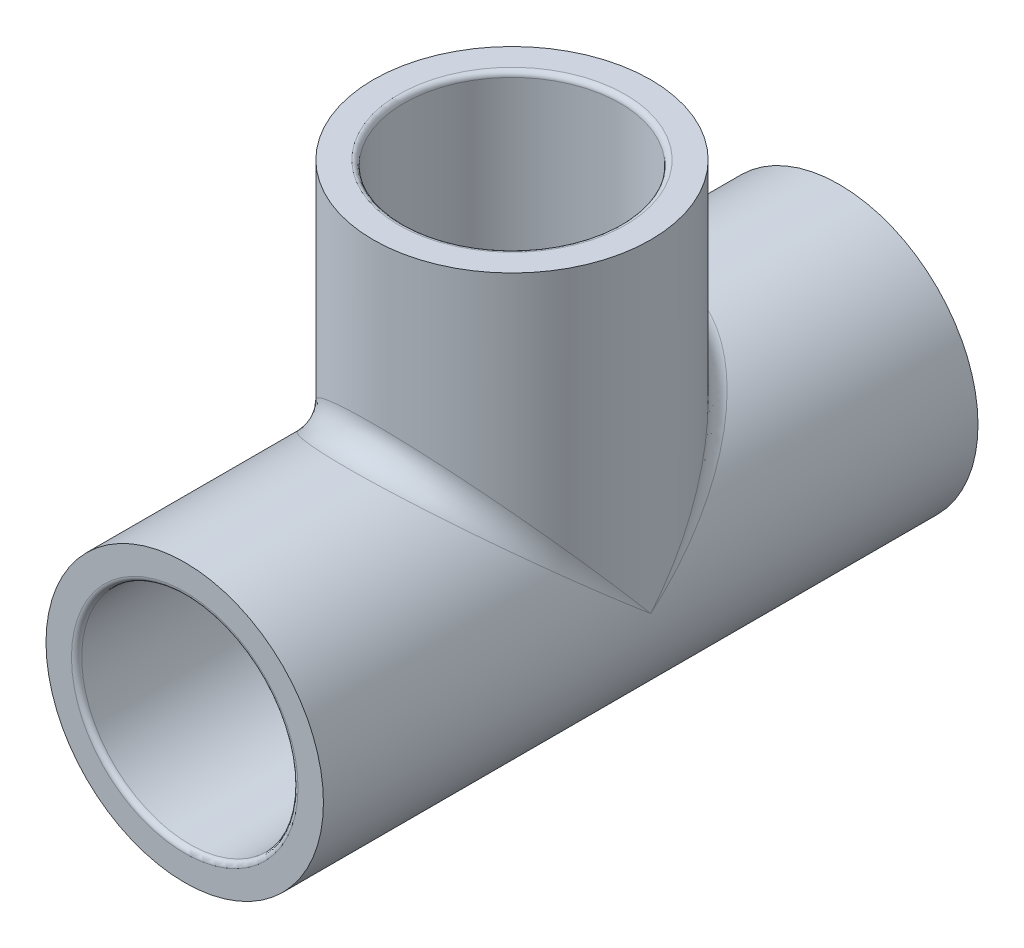
SolidWorks part; units mm, degrees
ref_plane "Front Plane" through (0, 0, 0) normal (0, 0, 1) x (1, 0, 0)
ref_plane "Top Plane" through (0, 0, 0) normal (0, 1, 0) x (1, 0, 0)
ref_plane "Right Plane" through (0, 0, 0) normal (1, 0, 0) x (0, 0, -1)
sketch "Sketch1" plane through (0, 0, 0) normal (0, 0, 1) x (1, 0, 0)
  circle A0 centre (0, 0) radius 10.6934
  circle A1 centre (0, 0) radius 13.716
  dimension "D1" = 21.3868
  dimension "D2" = 27.432
extrude "Boss-Extrude1" add sketch "Sketch1" along normal blind 64.7192
ref_plane "Plane1" through (0, 0, 32.3596) normal (0, 0, 1) x (1, 0, 0)
sketch "Sketch2" plane through (0, 0, 0) normal (0, 1, 0) x (1, 0, 0)
  line L0 (-15.0876, -32.3596) -> (15.0876, -32.3596) construction
  circle A0 centre (0, -32.3596) radius 13.716
  circle A1 centre (0, -32.3596) radius 10.6934
  dimension "D1" = 27.432
  dimension "D2" = 21.3868
extrude "Boss-Extrude2" add sketch "Sketch2" along normal blind 32.004
sketch "Sketch6" plane through (0, 0, 0) normal (0, 1, 0) x (1, 0, 0)
  circle A0 centre (0, -32.3596) radius 9.9314
  circle A1 centre (0, -32.3596) radius 10.6934 construction
  circle A2 centre (0, -32.3596) radius 10.6934
  dimension "D1" = 0.762
extrude "Boss-Extrude4" add sketch "Sketch6" along normal blind 17.1958
sketch "Sketch7" plane through (0, 0, 64.7192) normal (0, 0, 1) x (1, 0, 0)
  circle A0 centre (0, 0) radius 10.6934
extrude "Cut-Extrude2" cut sketch "Sketch7" against normal through all
sketch "Sketch8" plane through (0, 32.004, 0) normal (0, 1, 0) x (1, 0, 0)
  line L0 (-15.0876, -32.3596) -> (15.0876, -32.3596) construction
  circle A0 centre (0, -32.3596) radius 10.6934
extrude "Cut-Extrude3" cut sketch "Sketch8" against normal blind 19.431
sketch "Sketch9" plane through (0, 0, 32.3596) normal (0, 0, 1) x (1, 0, 0)
  circle A0 centre (0, 0) radius 9.9314
  circle A2 centre (0, 0) radius 10.6934
extrude "Boss-Extrude5" add sketch "Sketch9" along normal mid plane 25.4 separate body
sketch "Sketch10" plane through (0, 32.004, 0) normal (0, 1, 0) x (1, 0, 0)
  line L0 (-15.0876, -32.3596) -> (15.0876, -32.3596) construction
  circle A0 centre (0, -32.3596) radius 9.9314
  dimension "D1" = 19.8628
extrude "Cut-Extrude6" cut sketch "Sketch10" against normal blind 30.48
fillet "Fillet1" radius 0.508 3 edges at (10.6934, 0, 0) (10.6934, 0, 64.7192) (0, 32.004, 43.053)
fillet "Fillet2" radius 2.54 2 edges at (0, 13.716, 46.0756) (0, 13.716, 18.6436)
